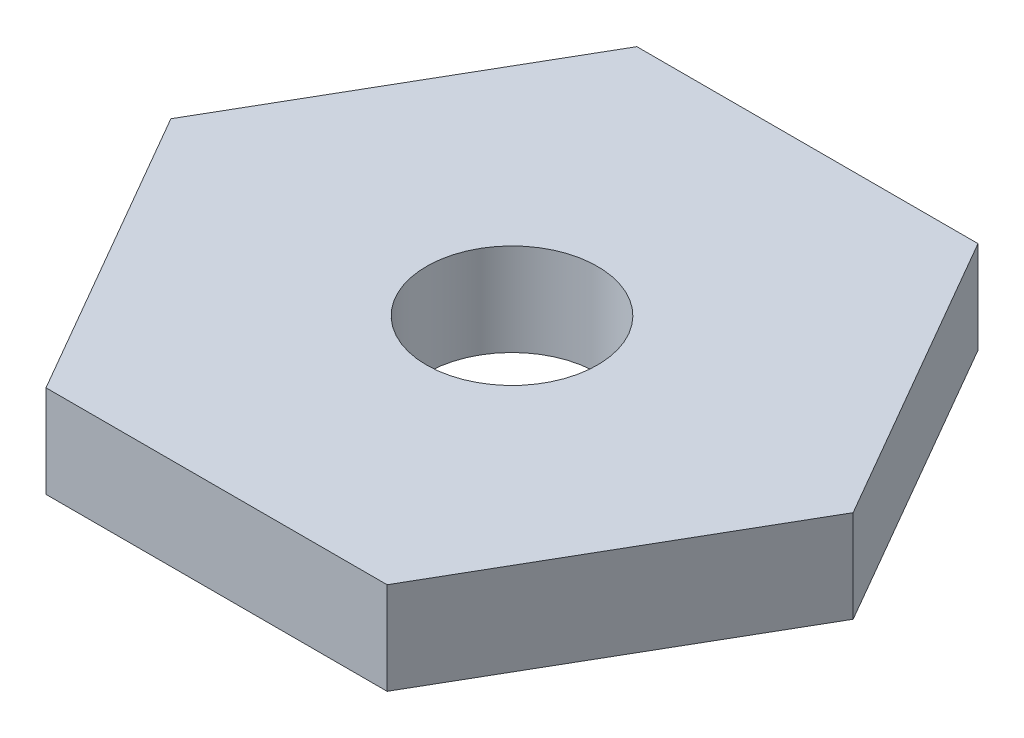
SolidWorks part; units mm, degrees
ref_plane "Plan de face" through (0, 0, 0) normal (0, 0, 1) x (1, 0, 0)
ref_plane "Plan de dessus" through (0, 0, 0) normal (0, 1, 0) x (1, 0, 0)
ref_plane "Plan de droite" through (0, 0, 0) normal (1, 0, 0) x (0, 0, -1)
sketch "Esquisse1" plane through (0, 0, 0) normal (0, 1, 0) x (1, 0, 0)
  line L1 (36.9504, 0) -> (18.4752, 32)
  line L2 (18.4752, 32) -> (-18.4752, 32)
  line L3 (-18.4752, 32) -> (-36.9504, 0)
  line L4 (-36.9504, 0) -> (-18.4752, -32)
  line L5 (-18.4752, -32) -> (18.4752, -32)
  line L6 (18.4752, -32) -> (36.9504, 0)
  circle A0 centre (0, 0) radius 32 construction
  circle A1 centre (0, 0) radius 9.2594
  dimension "D1" = 32
extrude "Boss.-Extru.1" add sketch "Esquisse1" along normal blind 10
